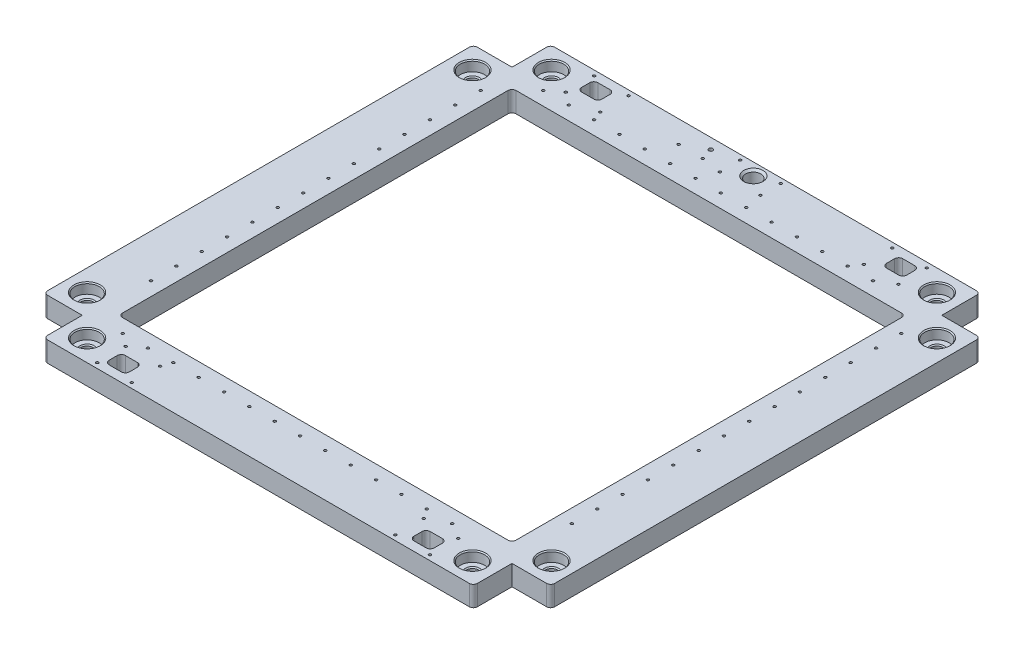
SolidWorks part; units mm, degrees
material "ASTM A36 Steel"
ref_plane "Front Plane" through (0, 0, 0) normal (0, 0, 1) x (1, 0, 0)
ref_plane "Top Plane" through (0, 0, 0) normal (0, 1, 0) x (1, 0, 0)
ref_plane "Right Plane" through (0, 0, 0) normal (1, 0, 0) x (0, 0, -1)
sketch "Sketch1" plane through (0, 0, 0) normal (0, 1, 0) x (1, 0, 0)
  line L1 (250, -250) -> (-250, -250)
  line L2 (250, -250) -> (250, 250)
  line L3 (250, 250) -> (-250, 250)
  line L4 (-250, -250) -> (-250, 250)
  line L5 (250, -250) -> (-250, 250) construction
  line L6 (250, 250) -> (-250, -250) construction
  point P0 (0, 0)
  dimension "D1" = 500
  dimension "D2" = 500
extrude "Boss-Extrude1" add sketch "Sketch1" along normal blind 20
sketch "Sketch2" plane through (0, 20, 0) normal (0, 1, 0) x (1, 0, 0)
  line L0 (250, 250) -> (-250, 250) construction
  line L10 (-250, 250) -> (-250, -250) construction
  line L15 (-250, 169) -> (-208, 169)
  line L16 (-250, 169) -> (-250, 211)
  line L17 (-174.5, 213.5) -> (-205.5, 213.5)
  line L27 (-250, 211) -> (-208, 211)
  line L33 (-208, 169) -> (-208, 211)
  line L35 (-250, 169) -> (-208, 211) construction
  line L36 (-250, 211) -> (-208, 169) construction
  line L37 (-169, 208) -> (-211, 208)
  line L38 (-169, 208) -> (-169, 250)
  line L39 (-169, 250) -> (-211, 250)
  line L40 (-211, 208) -> (-211, 250)
  line L41 (-169, 208) -> (-211, 250) construction
  line L42 (-169, 250) -> (-211, 208) construction
  line L43 (-208, 206) -> (-213, 211)
  line L44 (-174.5, 213.5) -> (-174.5, 244.5)
  line L45 (-174.5, 244.5) -> (-205.5, 244.5)
  line L46 (-205.5, 213.5) -> (-205.5, 244.5)
  line L47 (-174.5, 213.5) -> (-205.5, 244.5) construction
  line L48 (-174.5, 244.5) -> (-205.5, 213.5) construction
  line L49 (-213.5, 174.5) -> (-244.5, 174.5)
  line L50 (-213.5, 174.5) -> (-213.5, 205.5)
  line L51 (-213.5, 205.5) -> (-244.5, 205.5)
  line L52 (-244.5, 174.5) -> (-244.5, 205.5)
  line L53 (-213.5, 174.5) -> (-244.5, 205.5) construction
  line L54 (-213.5, 205.5) -> (-244.5, 174.5) construction
  line L55 (-206, 208) -> (-211, 213)
  line L56 (-213, 211) -> (-211, 213) construction
  point P1 (-229, 190)
  point P5 (-190, 229)
  point P23 (-229, 190)
  point P27 (-190, 229)
  dimension "D1" = 5
  dimension "D2" = 45
  dimension "D3" = 42
  dimension "D4" = 31
  dimension "D5" = 45
  dimension "D6" = 5
  dimension "D7" = 60
hole_wizard "Bearing Press Fit" positions "Sketch8" profile "Sketch9" hole size "Ø12.0" standard "ANSI Metric" end condition through all
sketch "Sketch8" plane through (0, 20, 0) normal (0, 1, 0) x (1, 0, 0)
  line L1 (-169, 250) -> (-211, 208) construction
  point P8 (-190, 229)
  point P12 (-229, 190)
sketch "Sketch9" plane through (-190, 20, -229) normal (1, 0, 0) x (0, 0, 1)
  line L0 (0, 0) -> (0, 20)
  line L1 (0, 20) -> (6, 20)
  line L2 (6, 20) -> (6, 0)
  line L5 (6, 0) -> (0, 0)
  line L11 (0, -6.35) -> (0, 107.95) construction
  dimension "Thru Hole Dia." = 12
  dimension "Thru Hole Depth" = 20
ref_axis "Axis1" through (0, 21, 0) along (0, -1, 0)
pattern_circular "CirPattern1" count 4 over 360 about axis through (0, 21, 0) along (0, -1, 0) of "Bearing Press Fit"
sketch "Sketch5" plane through (0, 20, 0) normal (0, 1, 0) x (1, 0, 0)
  line L1 (194, -194) -> (-194, -194)
  line L2 (194, -194) -> (194, 194)
  line L3 (194, 194) -> (-194, 194)
  line L4 (-194, -194) -> (-194, 194)
  line L5 (194, -194) -> (-194, 194) construction
  line L6 (194, 194) -> (-194, -194) construction
  point P0 (0, 0)
  dimension "D1" = 388
extrude "Cut-Extrude1" cut sketch "Sketch5" against normal up to surface (20 mm away) up to face at (-229, 0, 196)
sketch "Sketch10" plane through (0, 0, 0) normal (0, 1, 0) x (1, 0, 0)
  line L5 (194, 194) -> (-194, 194) construction
  line L6 (214, -214) -> (-214, -214)
  line L14 (214, -214) -> (214, 214)
  line L15 (214, 214) -> (-214, 214)
  line L16 (-214, -214) -> (-214, 214)
  line L17 (214, -214) -> (-214, 214) construction
  line L18 (214, 214) -> (-214, -214) construction
  line L19 (201.5, -201.5) -> (-201.5, -201.5)
  line L20 (201.5, -201.5) -> (201.5, 201.5)
  line L21 (201.5, 201.5) -> (-201.5, 201.5)
  line L22 (-201.5, -201.5) -> (-201.5, 201.5)
  line L23 (201.5, -201.5) -> (-201.5, 201.5) construction
  line L24 (201.5, 201.5) -> (-201.5, -201.5) construction
  point P0 (0, 0)
  point P6 (0, 0)
  dimension "D2" = 7.5
  dimension "D1" = 12.5
extrude "Linear Rail Slot" cut sketch "Sketch10" along normal blind 2.5
fillet "Fillet2" radius 4 4 edges at (-194, 10, 194) (194, 10, 194) (194, 10, -194) (-194, 10, -194)
sketch "Sketch11" plane through (0, 2.5, 0) normal (0, -1, 0) x (1, 0, 0)
  line L0 (-194, 207.5) -> (166, 207.5)
  line L1 (-201.5, 201.5) -> (201.5, 201.5) construction
  line L3 (-214, -214) -> (-214, 214) construction
  point P16 (148.5, 207.5)
  point P18 (123.5, 207.5)
  point P19 (98.5, 207.5)
  point P20 (73.5, 207.5)
  point P21 (48.5, 207.5)
  point P22 (23.5, 207.5)
  point P23 (-1.5, 207.5)
  point P24 (-26.5, 207.5)
  point P25 (-51.5, 207.5)
  point P26 (-76.5, 207.5)
  point P28 (-101.5, 207.5)
  point P29 (-126.5, 207.5)
  point P30 (-151.5, 207.5)
  point P31 (-176.5, 207.5)
  dimension "D1" = 360
  dimension "D2" = 6
  dimension "D4" = 14
  dimension "D5" = 25
  dimension "D6" = 20
  dimension "D3" = 17.5
hole_wizard "Tap Drill for M3x0.5 Tap1" positions "Sketch12" profile "Sketch13" hole size "M3x0.5" standard "ANSI Metric" end condition through all
sketch "Sketch12" plane through (0, 2.5, 0) normal (0, -1, 0) x (-1, 0, 0)
  line L0 (194, -207.5) -> (-166, -207.5) construction
  point P28 (-148.5, -207.5)
  point P31 (-123.5, -207.5)
  point P34 (-98.5, -207.5)
  point P37 (-73.5, -207.5)
  point P40 (-48.5, -207.5)
  point P43 (-23.5, -207.5)
  point P46 (1.5, -207.5)
  point P49 (26.5, -207.5)
  point P51 (51.5, -207.5)
  point P54 (76.5, -207.5)
  point P57 (101.5, -207.5)
  point P61 (126.5, -207.5)
  point P64 (151.5, -207.5)
  point P67 (176.5, -207.5)
sketch "Sketch13" plane through (148.5, 2.5, 207.5) normal (1, 0, 0) x (0, 0, -1)
  line L0 (0, 0) -> (0, 17.5)
  line L1 (0, 17.5) -> (1.25, 17.5)
  line L2 (1.25, 17.5) -> (1.25, 0)
  line L5 (1.25, 0) -> (0, 0)
  line L11 (0, -6.35) -> (0, 107.95) construction
  dimension "Thru Hole Dia." = 2.5
  dimension "Thru Hole Depth" = 17.5
sketch "Sketch14" plane through (0, 0, 0) normal (0, -1, 0) x (1, 0, 0)
  line L1 (-151.5, 213.5) -> (-176.5, 213.5)
  line L2 (-147.5, 217.5) -> (-147.5, 219.5)
  line L3 (-151.5, 223.5) -> (-176.5, 223.5)
  line L4 (-180.5, 217.5) -> (-180.5, 219.5)
  line L5 (-147.5, 213.5) -> (-180.5, 223.5) construction
  line L6 (-147.5, 223.5) -> (-180.5, 213.5) construction
  line L7 (-201.5, 201.5) -> (201.5, 201.5) construction
  line L8 (-176.5, 207.5) -> (-151.5, 207.5) construction
  line L19 (-1.5, 213.5) -> (-26.5, 213.5)
  line L25 (2.5, 217.5) -> (2.5, 219.5)
  line L26 (-1.5, 223.5) -> (-26.5, 223.5)
  line L31 (-30.5, 217.5) -> (-30.5, 219.5)
  line L32 (2.5, 213.5) -> (-30.5, 223.5) construction
  line L33 (2.5, 223.5) -> (-30.5, 213.5) construction
  line L34 (-26.5, 207.5) -> (-1.5, 207.5) construction
  line L35 (148.5, 213.5) -> (123.5, 213.5)
  line L36 (152.5, 217.5) -> (152.5, 219.5)
  line L37 (148.5, 223.5) -> (123.5, 223.5)
  line L38 (119.5, 217.5) -> (119.5, 219.5)
  line L39 (152.5, 213.5) -> (119.5, 223.5) construction
  line L40 (152.5, 223.5) -> (119.5, 213.5) construction
  line L41 (123.5, 207.5) -> (148.5, 207.5) construction
  arc A3 (-147.5, 219.5) -> (-151.5, 223.5) centre (-151.5, 219.5) ccw
  arc A4 (-151.5, 213.5) -> (-147.5, 217.5) centre (-151.5, 217.5) ccw
  arc A5 (-176.5, 213.5) -> (-180.5, 217.5) centre (-176.5, 217.5) cw
  arc A6 (-176.5, 223.5) -> (-180.5, 219.5) centre (-176.5, 219.5) ccw
  arc A7 (2.5, 219.5) -> (-1.5, 223.5) centre (-1.5, 219.5) ccw
  arc A8 (-1.5, 213.5) -> (2.5, 217.5) centre (-1.5, 217.5) ccw
  arc A9 (-26.5, 213.5) -> (-30.5, 217.5) centre (-26.5, 217.5) cw
  arc A10 (-26.5, 223.5) -> (-30.5, 219.5) centre (-26.5, 219.5) ccw
  arc A11 (152.5, 219.5) -> (148.5, 223.5) centre (148.5, 219.5) ccw
  arc A12 (148.5, 213.5) -> (152.5, 217.5) centre (148.5, 217.5) ccw
  arc A13 (123.5, 213.5) -> (119.5, 217.5) centre (123.5, 217.5) cw
  arc A14 (123.5, 223.5) -> (119.5, 219.5) centre (123.5, 219.5) ccw
  point P0 (-164, 218.5)
  point P12 (-164, 207.5)
  point P26 (-14, 218.5)
  point P45 (136, 218.5)
  dimension "D5" = 3
  dimension "D4" = 4
  dimension "D1" = 33
  dimension "D2" = 12
  dimension "D3" = 10
  dimension "D7" = 25
  dimension "D6" = 150
mirror "Mirror5" about plane through (0, 0, 0) normal (0, 0, 1) of "Tap Drill for M3x0.5 Tap1"
ref_plane "Plane1" through (0, 0, 0) normal (-0.7071, 0, 0.7071) x (0.7071, 0, 0.7071)
mirror "Mirror6" about plane through (0, 0, 0) normal (-0.7071, 0, 0.7071) of "Mirror5"
sketch "Sketch19" plane through (0, 2.5, 0) normal (0, -1, 0) x (1, 0, 0)
  line L0 (-198.5, 201.5) -> (-198.5, 214)
  line L1 (-201.5, 201.5) -> (201.5, 201.5) construction
  line L2 (-214, 214) -> (214, 214) construction
  line L3 (-198.5, 214) -> (-214, 214)
  line L4 (-214, 214) -> (-214, 198.5)
  line L5 (-214, -214) -> (-214, 214) construction
  line L6 (-214, 198.5) -> (-201.5, 198.5)
  line L7 (-201.5, -201.5) -> (-201.5, 201.5) construction
  line L8 (-201.5, 198.5) -> (-201.5, 201.5)
  line L9 (-201.5, 201.5) -> (-198.5, 201.5)
  dimension "D1" = 3
extrude "Boss-Extrude2" add sketch "Sketch19" along normal up to surface (2.5 mm away) up to face at (-229, 0, 196)
pattern_circular "CirPattern4" count 4 over 360 about axis through (0, 21, 0) along (0, -1, 0) of "Boss-Extrude2"
sketch "Sketch20" plane through (0, 20, 0) normal (0, 1, 0) x (1, 0, 0)
  line L5 (-250, -250) -> (250, -250) construction
  line L20 (140.3, -225) -> (160.3, -241) construction
  line L23 (160.3, -225) -> (140.3, -241) construction
  line L28 (114, -247) -> (164, -219) construction
  line L29 (164, -247) -> (114, -219) construction
  line L30 (164, -219) -> (114, -219) construction
  line L31 (114, -247) -> (114, -219) construction
  line L32 (164, -247) -> (114, -247) construction
  line L33 (164, -247) -> (164, -219) construction
  line L34 (156.3, -241) -> (144.3, -241)
  line L35 (140.3, -229) -> (140.3, -237)
  line L36 (156.3, -225) -> (144.3, -225)
  line L37 (160.3, -229) -> (160.3, -237)
  arc A12 (144.3, -225) -> (140.3, -229) centre (144.3, -229) ccw
  arc A13 (140.3, -237) -> (144.3, -241) centre (144.3, -237) ccw
  arc A14 (160.3, -237) -> (156.3, -241) centre (156.3, -237) cw
  arc A15 (160.3, -229) -> (156.3, -225) centre (156.3, -229) ccw
  circle A16 centre (190, -229) radius 6 construction
  point P65 (150.3, -233)
  point P66 (139, -233)
  point P67 (139, -233)
  dimension "D7" = 39.7
  dimension "D8" = 11.3
  dimension "D6" = 4
  dimension "D1" = 28
  dimension "D2" = 50
  dimension "D3" = 17
  dimension "D4" = 20
  dimension "D5" = 16
extrude "Cut-Extrude3" cut sketch "Sketch20" against normal through all
hole_wizard "Tap Drill for M3x0.5 Tap6" positions "Sketch39" profile "Sketch40" hole size "M3x0.5" standard "ANSI Metric"
sketch "Sketch39" plane through (0, 20, 0) normal (0, 1, 0) x (1, 0, 0)
  line L1 (164, -245) -> (130, -245)
  line L2 (164, -245) -> (164, -217)
  line L3 (164, -217) -> (130, -217)
  line L4 (130, -245) -> (130, -217)
  line L5 (-250, -250) -> (250, -250) construction
  circle A0 centre (190, -229) radius 6 construction
  point P1 (164, -245)
  point P2 (130, -217)
  point P99 (164, -217)
  point P100 (130, -245)
  dimension "D1" = 34
  dimension "D2" = 28
  dimension "D3" = 5
  dimension "D4" = 26
sketch "Sketch40" plane through (164, 20, 245) normal (1, 0, 0) x (0, 0, 1)
  line L0 (0, 0) -> (0, 20)
  line L1 (0, 20) -> (1.25, 20)
  line L2 (1.25, 20) -> (1.25, 0)
  line L5 (1.25, 0) -> (0, 0)
  line L10 (0, 20) -> (-1.25, 20) construction
  line L11 (0, -6.35) -> (0, 107.95) construction
  dimension "Hole Dia." = 2.5
  dimension "Hole Depth" = 20
  dimension "Drill Angle" = 180
mirror "Mirror8" about plane through (0, 0, 0) normal (1, 0, 0) of "Tap Drill for M3x0.5 Tap6", "Cut-Extrude3"
mirror "Mirror9" about plane through (0, 0, 0) normal (0, 0, 1) of "Mirror8"
sketch "Sketch27" plane through (0, 20, 0) normal (0, 1, 0) x (1, 0, 0)
  line L1 (250, -250) -> (211.9, -250)
  line L2 (250, -250) -> (250, -211.9)
  line L3 (250, -211.9) -> (211.9, -211.9)
  line L4 (211.9, -250) -> (211.9, -211.9)
  dimension "D1" = 38.1
extrude "Cut-Extrude4" cut sketch "Sketch27" against normal up to surface (20 mm away) up to face at (164, 0, -243.75)
pattern_circular "CirPattern3" count 4 over 360 about axis through (0, 21, 0) along (0, -1, 0) of "Cut-Extrude4"
fillet "Fillet5" radius 4 16 edges at (198.5, 1.25, 214) (198.5, 1.25, 201.5) (201.5, 1.25, 198.5) (214, 1.25, 198.5) (-214, 1.25, 198.5) (-198.5, 1.25, 214) (-201.5, 1.25, 198.5) (-198.5, 1.25, 201.5) (-214, 1.25, -198.5) (-198.5, 1.25, -214) (-198.5, 1.25, -201.5) (-201.5, 1.25, -198.5) (198.5, 1.25, -201.5) (198.5, 1.25, -214) (201.5, 1.25, -198.5) (214, 1.25, -198.5)
hole_wizard "Tap Drill for M3x0.5 Tap4" positions "Sketch35" profile "Sketch36" hole size "M3x0.5" standard "ANSI Metric" end condition up to next
sketch "Sketch35" plane through (0, 20, 0) normal (0, 1, 0) x (1, 0, 0)
  line L1 (20, 225) -> (-20, 225)
  line L2 (20, 225) -> (20, 245)
  line L3 (20, 245) -> (-20, 245)
  line L4 (-20, 225) -> (-20, 245)
  line L5 (20, 225) -> (-20, 245) construction
  line L6 (20, 245) -> (-20, 225) construction
  line L7 (211.9, 250) -> (-211.9, 250) construction
  point P2 (-20, 245)
  point P53 (20, 225)
  point P54 (20, 245)
  point P55 (-20, 225)
  point P69 (0, 235)
  dimension "D1" = 20
  dimension "D2" = 40
  dimension "D3" = 15
sketch "Sketch36" plane through (-20, 20, -245) normal (1, 0, 0) x (0, 0, 1)
  line L0 (0, 0) -> (0, 20)
  line L1 (0, 20) -> (1.25, 20)
  line L2 (1.25, 20) -> (1.25, 0)
  line L5 (1.25, 0) -> (0, 0)
  line L11 (0, -6.35) -> (0, 107.95) construction
  dimension "Thru Hole Dia." = 2.5
  dimension "Thru Hole Depth" = 20
hole_wizard "Ø15.0 (15) Diameter Hole2" positions "Sketch37" profile "Sketch38" hole size "Ø15.0" standard "ANSI Metric" end condition up to next
sketch "Sketch37" plane through (0, 20, 0) normal (0, 1, 0) x (1, 0, 0)
  circle A0 centre (0, 235) radius 1.25 construction
  point P0 (0, 238)
  dimension "D1" = 3
sketch "Sketch38" plane through (0, 20, -238) normal (1, 0, 0) x (0, 0, 1)
  line L0 (0, 0) -> (0, 20)
  line L1 (0, 20) -> (7.5, 20)
  line L2 (7.5, 20) -> (7.5, 0)
  line L5 (7.5, 0) -> (0, 0)
  line L11 (0, -6.35) -> (0, 107.95) construction
  dimension "Thru Hole Dia." = 15
  dimension "Thru Hole Depth" = 20
chamfer "Chamfer1" distance 2 angle 45 2 edges at (0, 0, -230.5) (0, 20, -230.5)
hole_wizard "Ø24.0 (24) Diameter Hole1" positions "Sketch41" profile "Sketch42" hole size "Ø24.0" standard "ANSI Metric"
sketch "Sketch41" plane through (0, 20, 0) normal (0, 1, 0) x (1, 0, 0)
  point P0 (-229, -190)
  point P3 (-190, -229)
  point P6 (190, -229)
  point P9 (229, -190)
  point P12 (229, 190)
  point P15 (190, 229)
  point P18 (-190, 229)
  point P21 (-229, 190)
sketch "Sketch42" plane through (-229, 20, 190) normal (1, 0, 0) x (0, 0, 1)
  line L0 (0, 0) -> (0, 10)
  line L1 (0, 10) -> (12, 10)
  line L2 (12, 10) -> (12, 0)
  line L5 (12, 0) -> (0, 0)
  line L10 (0, 10) -> (-12, 10) construction
  line L11 (0, -6.35) -> (0, 107.95) construction
  dimension "Hole Dia." = 24
  dimension "Hole Depth" = 10
  dimension "Drill Angle" = 180
chamfer "Chamfer2" distance 1 angle 45 24 edges at (-229, 0, -184) (-229, 10, -196) (-190, 0, -223) (-190, 10, -235) (229, 0, -184) (229, 10, -196) (190, 0, -223) (190, 10, -235) (229, 0, 196) (229, 10, 184) (190, 0, 235) (190, 10, 223) (-190, 0, 235) (-190, 10, 223) (-229, 0, 196) (-229, 10, 184) (-229, 20, -178) (-190, 20, -217) (229, 20, -178) (190, 20, -217) (229, 20, 202) (190, 20, 241) (-190, 20, 241) (-229, 20, 202)
fillet "Fillet6" radius 4 8 edges at (250, 10, -211.9) (211.9, 10, -250) (-211.9, 10, -250) (-250, 10, -211.9) (211.9, 10, 250) (250, 10, 211.9) (-211.9, 10, 250) (-250, 10, 211.9)
hole_wizard "Tap Drill for M3x0.5 Tap7" positions "Sketch43" profile "Sketch44" hole size "M3x0.5" standard "ANSI Metric" end condition up to next
sketch "Sketch43" plane through (0, 20, 0) normal (0, 1, 0) x (1, 0, 0)
  line L0 (-63.7737, 228) -> (-39.7737, 228) construction
  line L2 (207.9, 250) -> (-207.9, 250) construction
  circle A0 centre (-20, 225) radius 1.25 construction
  point P1 (-63.7737, 228)
  point P2 (-39.7737, 228)
  dimension "D3" = 20
  dimension "D1" = 22
  dimension "D2" = 24
sketch "Sketch44" plane through (-63.7737, 20, -228) normal (1, 0, 0) x (0, 0, 1)
  line L0 (0, 0) -> (0, 20)
  line L1 (0, 20) -> (1.25, 20)
  line L2 (1.25, 20) -> (1.25, 0)
  line L5 (1.25, 0) -> (0, 0)
  line L11 (0, -6.35) -> (0, 107.95) construction
  dimension "Thru Hole Dia." = 2.5
  dimension "Thru Hole Depth" = 20
hole_wizard "Ø4.0 (4) Diameter Hole1" positions "Sketch45" profile "Sketch46" hole size "Ø4.0" standard "ANSI Metric" end condition up to next
sketch "Sketch45" plane through (0, 20, 0) normal (0, 1, 0) x (1, 0, 0)
  circle A0 centre (-63.7737, 228) radius 1.25 construction
  point P0 (-43.4737, 239.5)
  dimension "D1" = 20.3
  dimension "D2" = 11.5
sketch "Sketch46" plane through (-43.4737, 20, -239.5) normal (1, 0, 0) x (0, 0, 1)
  line L0 (0, 0) -> (0, 20)
  line L1 (0, 20) -> (2, 20)
  line L2 (2, 20) -> (2, 0)
  line L5 (2, 0) -> (0, 0)
  line L11 (0, -6.35) -> (0, 107.95) construction
  dimension "Thru Hole Dia." = 4
  dimension "Thru Hole Depth" = 20
